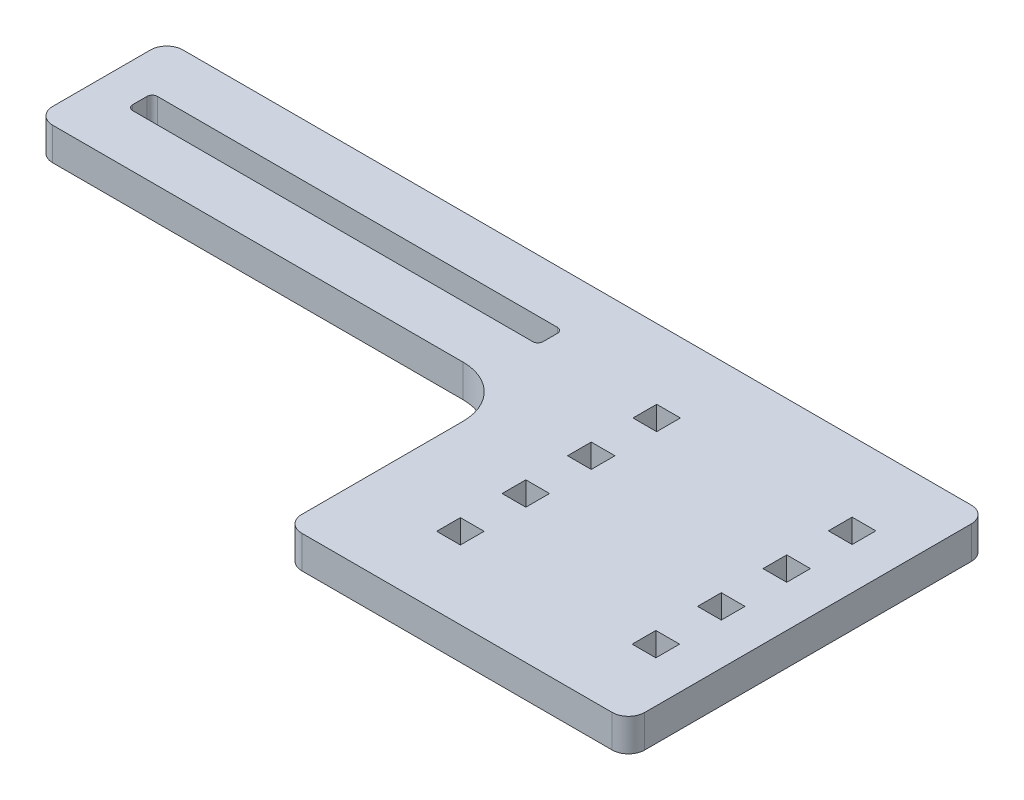
SolidWorks part; units mm, degrees
ref_plane "Front Plane" through (0, 0, 0) normal (0, 0, 1) x (1, 0, 0)
ref_plane "Top Plane" through (0, 0, 0) normal (0, 1, 0) x (1, 0, 0)
ref_plane "Right Plane" through (0, 0, 0) normal (1, 0, 0) x (0, 0, -1)
sketch "Sketch1" plane through (0, 0, 0) normal (0, 1, 0) x (1, 0, 0)
  line L0 (0, 0) -> (160, 0)
  line L1 (160, 0) -> (160, -70)
  line L2 (160, -70) -> (93.1472, -70)
  line L3 (93.1472, -70) -> (93.1472, -25.4)
  line L4 (93.1472, -25.4) -> (0, -25.4)
  line L5 (0, -25.4) -> (0, 0)
  line L6 (7.5, -10.3302) -> (87.5, -10.3302)
  line L11 (7.5, -10.3302) -> (7.5, -15.15)
  line L12 (7.5, -15.15) -> (87.5, -15.15)
  line L13 (87.5, -10.3302) -> (87.5, -15.15)
  line L58 (147.2472, -13.6493) -> (151.87, -13.6493)
  line L59 (151.87, -13.6493) -> (151.87, -18.2721)
  line L60 (147.2472, -18.2721) -> (151.87, -18.2721)
  line L61 (147.2472, -13.6493) -> (147.2472, -18.2721)
  line L66 (147.2472, -26.4021) -> (151.87, -26.4021)
  line L67 (151.87, -26.4021) -> (151.87, -31.0249)
  line L68 (147.2472, -31.0249) -> (151.87, -31.0249)
  line L69 (147.2472, -26.4021) -> (147.2472, -31.0249)
  line L74 (147.2472, -39.1549) -> (151.87, -39.1549)
  line L75 (151.87, -39.1549) -> (151.87, -43.7777)
  line L76 (147.2472, -43.7777) -> (151.87, -43.7777)
  line L77 (147.2472, -39.1549) -> (147.2472, -43.7777)
  line L86 (109.1472, -13.6493) -> (113.77, -13.6493)
  line L87 (113.77, -13.6493) -> (113.77, -18.2721)
  line L88 (109.1472, -18.2721) -> (113.77, -18.2721)
  line L89 (109.1472, -13.6493) -> (109.1472, -18.2721)
  line L90 (109.1472, -26.4021) -> (113.77, -26.4021)
  line L91 (113.77, -26.4021) -> (113.77, -31.0249)
  line L92 (109.1472, -31.0249) -> (113.77, -31.0249)
  line L93 (109.1472, -26.4021) -> (109.1472, -31.0249)
  line L94 (109.1472, -39.1549) -> (113.77, -39.1549)
  line L95 (113.77, -39.1549) -> (113.77, -43.7777)
  line L96 (109.1472, -43.7777) -> (113.77, -43.7777)
  line L97 (109.1472, -39.1549) -> (109.1472, -43.7777)
  line L99 (151.87, -51.9077) -> (147.2472, -51.9077)
  line L100 (151.87, -51.9077) -> (151.87, -56.5305)
  line L101 (151.87, -56.5305) -> (147.2472, -56.5305)
  line L102 (147.2472, -51.9077) -> (147.2472, -56.5305)
  line L103 (113.77, -56.5305) -> (109.1472, -56.5305)
  line L104 (113.77, -56.5305) -> (113.77, -51.9077)
  line L105 (113.77, -51.9077) -> (109.1472, -51.9077)
  line L106 (109.1472, -56.5305) -> (109.1472, -51.9077)
  dimension "D2" = 25.4
  dimension "D3" = 16
  dimension "D4" = 70
  dimension "D5" = 10.25
  dimension "D6" = 7.5
  dimension "D11" = 4.6228
  dimension "D12" = 8.13
  dimension "D13" = 8.13
  dimension "D14" = 33.4772
  dimension "D15" = 8.13
  dimension "D16" = 160
  dimension "D17" = 8.13
  dimension "D10" = 80
extrude "Boss-Extrude1" add sketch "Sketch1" along normal blind 6.35
fillet "Fillet2" radius 3.175 1 edges at (0, 3.175, 25.4)
fillet "Fillet3" radius 3.175 4 edges at (93.1472, 3.175, 70) (160, 3.175, 70) (160, 3.175, 0) (0, 3.175, 0)
sketch "Sketch3" plane through (0, 6.35, 0) normal (0, 1, 0) x (1, 0, 0)
  line L0 (151.87, -18.2721) -> (147.2472, -13.6493) construction
  line L1 (151.87, -18.2721) -> (147.2472, -18.2721)
  line L2 (151.87, -18.2721) -> (151.87, -13.6493)
  line L3 (151.87, -13.6493) -> (147.2472, -13.6493)
  line L4 (147.2472, -18.2721) -> (147.2472, -13.6493)
  line L5 (113.77, -18.2721) -> (109.1472, -18.2721)
  line L6 (113.77, -18.2721) -> (113.77, -13.6493)
  line L7 (113.77, -13.6493) -> (109.1472, -13.6493)
  line L8 (109.1472, -18.2721) -> (109.1472, -13.6493)
  line L9 (147.2472, -18.2721) -> (151.87, -13.6493) construction
  line L10 (113.77, -18.2721) -> (109.1472, -13.6493) construction
  line L11 (109.1472, -18.2721) -> (113.77, -13.6493) construction
  circle A0 centre (111.4586, -15.9607) radius 3.2688
  circle A1 centre (149.5586, -15.9607) radius 3.2688
fillet "Fillet4" radius 10 1 edges at (93.1472, 3.175, 25.4)
fillet "Fillet5" radius 1 4 edges at (87.5, 3.175, 15.15) (87.5, 3.175, 10.3302) (7.5, 3.175, 10.3302) (7.5, 3.175, 15.15)
